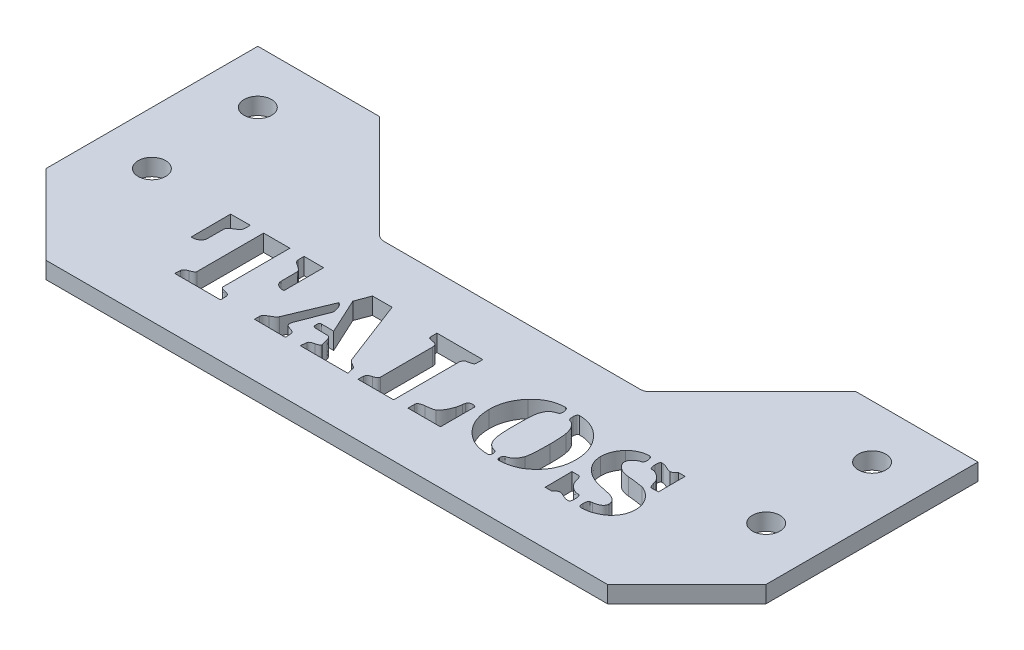
SolidWorks part; units mm, degrees
material "6061-T6 (SS)"
ref_plane "Front Plane" through (0, 0, 0) normal (0, 0, 1) x (1, 0, 0)
ref_plane "Top Plane" through (0, 0, 0) normal (0, 1, 0) x (1, 0, 0)
ref_plane "Right Plane" through (0, 0, 0) normal (1, 0, 0) x (0, 0, -1)
sketch "Sketch1" plane through (0, 0, 0) normal (0, 1, 0) x (1, 0, 0)
  line L0 (-48, 40) -> (-48, 30)
  line L1 (68, 0) -> (-68, 0)
  line L2 (68, 40) -> (68, 0)
  line L3 (48, 40) -> (68, 40)
  line L4 (48, 40) -> (48, 30)
  line L5 (48, 30) -> (38, 20)
  line L8 (-38, 20) -> (38, 20)
  line L9 (-58, 40) -> (-58, 0) construction
  line L10 (-68, 20) -> (0, 20) construction
  line L13 (0, 0) -> (0, 20) construction
  line L14 (-48, 40) -> (-68, 40)
  line L15 (-68, 40) -> (-68, 0)
  line L16 (-48, 30) -> (-38, 20)
  line L19 (-38, 20) -> (0, 20) construction
  circle A0 centre (-58, 10) radius 2.6
  circle A1 centre (-58, 30) radius 2.6
  circle A3 centre (58, 10) radius 2.6
  circle A4 centre (58, 30) radius 2.6
  dimension "D4" = 20
  dimension "D5" = 5.2
  dimension "D2" = 40
  dimension "D3" = 20
  dimension "D6" = 136
  dimension "D8" = 10
extrude "Boss-Extrude1" add sketch "Sketch1" along normal blind 3.175
sketch "Sketch2" plane through (0, 3.175, 0) normal (0, 1, 0) x (1, 0, 0)
  line L0 (-58, 10) -> (-58, -5) construction
  line L1 (-58, -5) -> (58, -5) construction
  line L2 (58, -5) -> (58, 10) construction
  text T0 "TALOS" font "Lintsec" height 15
  dimension "D1" = 15
sketch "Sketch3" plane through (0, 3.175, 0) normal (0, 1, 0) x (1, 0, 0)
  line L0 (-68, 0) -> (-53, -15)
  line L1 (-53, -15) -> (53, -15)
  line L2 (0, 0) -> (0, -15) construction
  line L5 (-38, 20) -> (-48, 30) construction
  line L6 (-58, -5) -> (58, -5) construction
  line L7 (68, 0) -> (53, -15)
  line L8 (-68, 0) -> (68, 0) construction
  line L9 (-68, 0) -> (68, 0)
  dimension "D1" = 10
extrude "Boss-Extrude2" add sketch "Sketch3" against normal up to surface (3.175 mm away) up to face at (-58, 0, -7.4)
extrude "Cut-Extrude1" cut sketch "Sketch2" against normal up to surface (3.175 mm away) up to face at (-58, 0, -7.4)
sketch "Sketch4" plane through (0, 3.175, 0) normal (0, 1, 0) x (1, 0, 0)
  line L0 (-48, 40) -> (-48, 30)
  line L1 (-48, 30) -> (-38, 20)
  line L2 (-38, 20) -> (-28, 20)
  line L3 (38, 20) -> (-38, 20) construction
  line L4 (-48, 40) -> (-45, 40)
  line L5 (-45, 40) -> (-28, 23)
  line L6 (-28, 23) -> (-28, 20)
  line L7 (0, 20) -> (0, 0) construction
  line L9 (-28, 23) -> (-25.5858, 20.5858)
  line L10 (28, 20) -> (24.1716, 20)
  line L11 (-28, 20) -> (-24.1716, 20)
  line L12 (28, 23) -> (25.5858, 20.5858)
  line L13 (28, 23) -> (28, 20)
  line L14 (45, 40) -> (28, 23)
  line L15 (48, 40) -> (45, 40)
  line L16 (38, 20) -> (28, 20)
  line L17 (48, 30) -> (38, 20)
  line L18 (48, 40) -> (48, 30)
  arc A0 (-25.5858, 20.5858) -> (-24.1716, 20) centre (-24.1716, 22) ccw
  arc A1 (25.5858, 20.5858) -> (24.1716, 20) centre (24.1716, 22) cw
  dimension "D4" = 2
  dimension "D1" = 3
  dimension "D2" = 45
  dimension "D3" = 3
extrude "Boss-Extrude3" add sketch "Sketch4" against normal up to surface (3.175 mm away) contours L6 L5 L4 | A0 L9 L6 | L12 A1 L13 | L15 L14 L13 region at (-39.425, 3.175, -28.575) region at (-26.9615, 3.175, -20.9835) region at (26.9615, 3.175, -20.9835) region at (39.425, 3.175, -28.575) up to face at (33.6533, 0, 3.2992)
